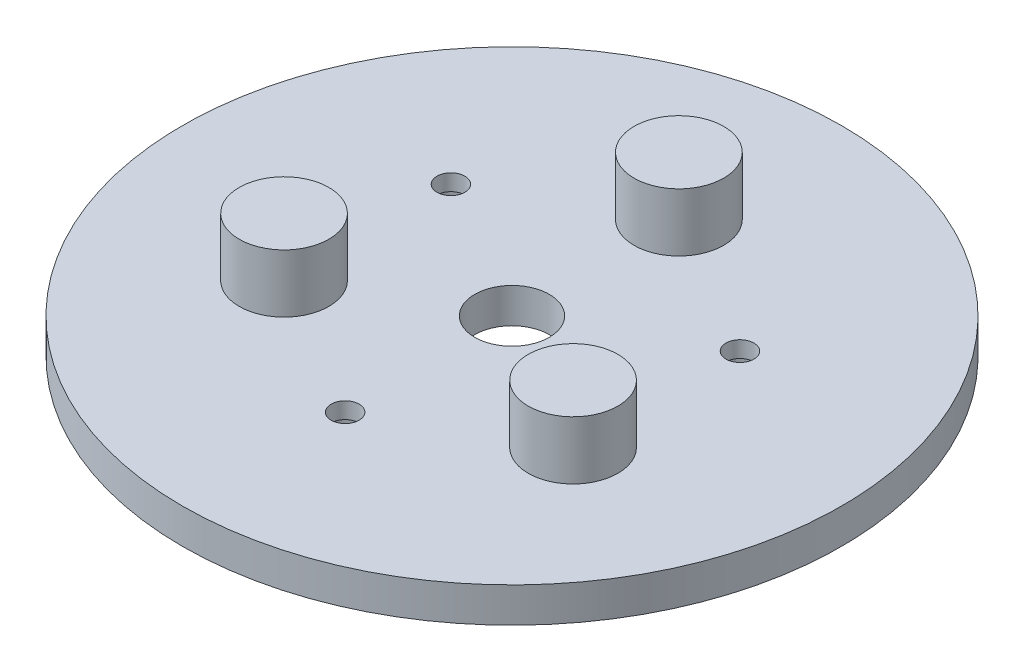
SolidWorks part; units mm, degrees
ref_plane "정면" through (0, 0, 0) normal (0, 0, 1) x (1, 0, 0)
ref_plane "윗면" through (0, 0, 0) normal (0, 1, 0) x (1, 0, 0)
ref_plane "우측면" through (0, 0, 0) normal (1, 0, 0) x (0, 0, -1)
sketch "스케치1" plane through (0, 0, 0) normal (0, 1, 0) x (1, 0, 0)
  line L0 (0, 14.33) -> (0, 23.13)
  line L1 (0, 0) -> (-12.4101, 7.165) construction
  line L2 (0, 0) -> (-12.4101, -7.165) construction
  line L3 (0, 0) -> (12.4101, 7.165) construction
  circle A0 centre (0, 0) radius 28.3
  circle A1 centre (0, 14.33) radius 3.85
  circle A2 centre (0, 0) radius 23.13 construction
  circle A3 centre (12.4101, -7.165) radius 3.85
  circle A4 centre (-12.4101, -7.165) radius 3.85
  circle A5 centre (0, -14.33) radius 0.5
  circle A6 centre (-12.4101, 7.165) radius 0.5
  circle A7 centre (12.4101, 7.165) radius 0.5
  point P6 (-12.4101, 7.165)
  point P7 (0, 14.33)
  point P8 (-12.4101, -7.165)
  point P14 (0, 0)
  point P15 (12.4101, -7.165)
  point P17 (12.4101, 7.165)
  point P18 (0, 0)
  point P21 (0, -14.33)
  point P22 (0, 0)
  dimension "D1" = 56.6
  dimension "D3" = 7.7
  dimension "D2" = 46.26
  dimension "D14" = 1
  dimension "D4" = 14.33
  dimension "D6" = 14.33
  dimension "D7" = 14.33
  dimension "D10" = 14.33
  dimension "D11" = 14.33
  dimension "D12" = 60
  dimension "D13" = 120
  dimension "D5" = 3
  dimension "D8" = 2
  dimension "D9" = 3
extrude "보스-돌출1" add sketch "스케치1" along normal blind 8 contours A1 | A3 | A4 region at (-2.6454, 0, -11.6846) region at (12.4101, 0, 7.165) region at (-12.4101, 0, 7.165)
extrude "보스-돌출2" add sketch "스케치1<3>" along normal blind 3 contours A0 A4 A3 A1 region at (0, 0, 0)
sketch "스케치1<3>" plane through (0, 0, 0) normal (0, 1, 0) x (1, 0, 0) same geometry as "스케치1"
sketch "스케치2" plane through (0, 3, 0) normal (0, 1, 0) x (1, 0, 0)
  circle A0 centre (0, 0) radius 3.2
  dimension "D1" = 6.4
extrude "컷-돌출1" cut sketch "스케치2" against normal through all
hole_wizard "M2 남비 머리 나사용 카운터보어1" positions "스케치6" profile "스케치7" counterbore size "M2" standard "ISO"
sketch "스케치6" plane through (0, 0, 0) normal (0, -1, 0) x (-1, 0, 0)
  point P0 (0, -14.33)
  point P3 (12.4101, 7.165)
  point P6 (-12.4101, 7.165)
sketch "스케치7" plane through (0, 0, 14.33) normal (1, 0, 0) x (0, 0, -1)
  line L0 (0, 0) -> (0, 3.721)
  line L1 (0, 3.721) -> (1.2, 3)
  line L2 (1.2, 3) -> (1.2, 1.6)
  line L3 (1.2, 1.6) -> (2.5, 1.6)
  line L4 (2.5, 1.6) -> (2.5, 0)
  line L5 (2.5, 0) -> (0, 0)
  line L10 (0, 3.721) -> (-1.2, 3) construction
  line L11 (0, -6.35) -> (0, 107.95) construction
  dimension "구멍 지름" = 2.4
  dimension "구멍 깊이" = 3
  dimension "카운터보어 지름" = 5
  dimension "카운터보어 깊이" = 1.6
  dimension "드릴 각도" = 118
